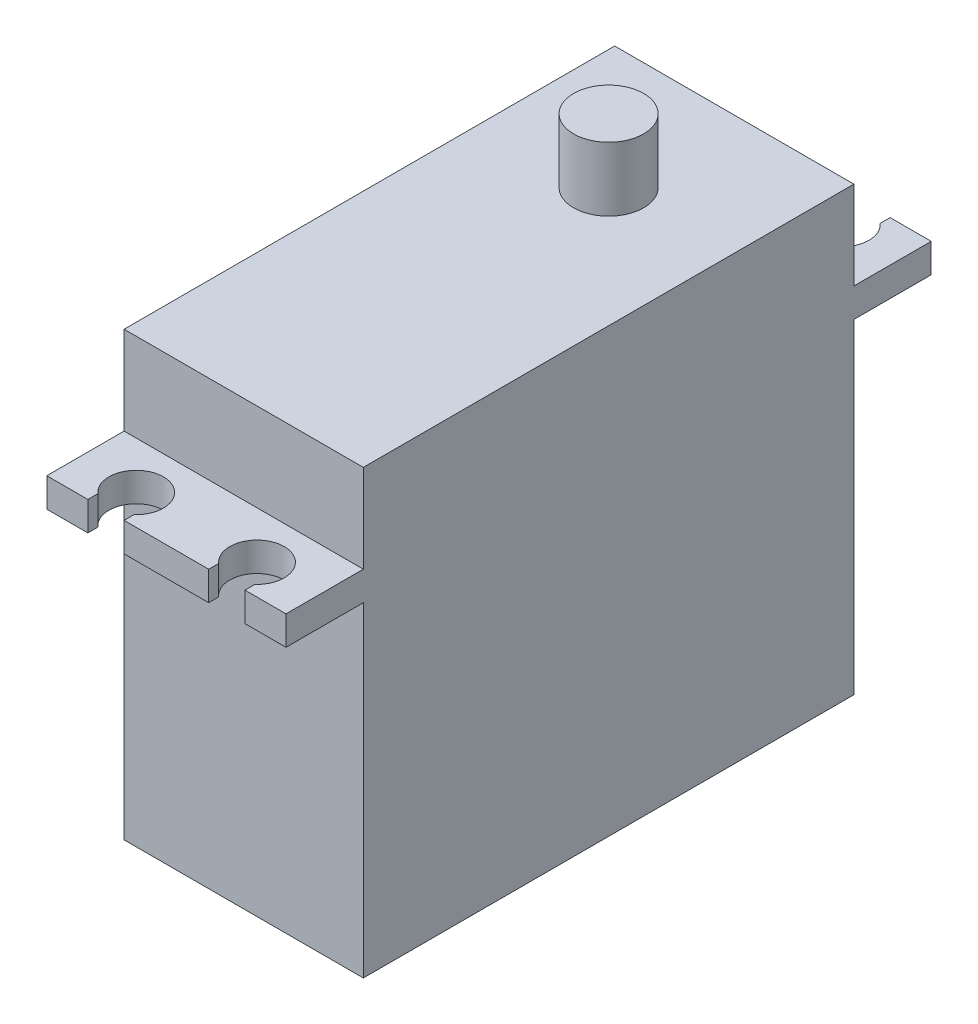
SolidWorks part; units mm, degrees
ref_plane "Front Plane" through (0, 0, 0) normal (0, 0, 1) x (1, 0, 0)
ref_plane "Top Plane" through (0, 0, 0) normal (0, 1, 0) x (1, 0, 0)
ref_plane "Right Plane" through (0, 0, 0) normal (1, 0, 0) x (0, 0, -1)
sketch "Sketch2" plane through (0, 0, 0) normal (1, 0, 0) x (0, 0, -1)
  line L1 (-20.3, 18.3) -> (20.3, 18.3)
  line L2 (-20.3, 18.3) -> (-20.3, -18.3)
  line L3 (-20.3, -18.3) -> (20.3, -18.3)
  line L4 (20.3, 18.3) -> (20.3, -18.3)
  line L5 (-20.3, 18.3) -> (20.3, -18.3) construction
  line L6 (-20.3, -18.3) -> (20.3, 18.3) construction
  line L7 (20.3, 11) -> (26.7, 11)
  line L8 (20.3, 11) -> (20.3, 8.6)
  line L9 (20.3, 8.6) -> (26.7, 8.6)
  line L10 (26.7, 11) -> (26.7, 8.6)
  line L11 (-20.3, 11) -> (-26.7, 11)
  line L12 (-20.3, 11) -> (-20.3, 8.6)
  line L13 (-20.3, 8.6) -> (-26.7, 8.6)
  line L14 (-26.7, 11) -> (-26.7, 8.6)
  line L16 (-26.7, 9.8) -> (26.7, 9.8) construction
  line L17 (7, 18.3) -> (12.8, 18.3)
  line L18 (7, 18.3) -> (7, 23.6)
  line L19 (7, 23.6) -> (12.8, 23.6)
  line L20 (12.8, 18.3) -> (12.8, 23.6)
  point P0 (0, 0)
  point P15 (9.9, 23.6)
  point P22 (0, 9.8)
  dimension "D1" = 26.9
  dimension "D2" = 40.6
  dimension "D3" = 5.3
  dimension "D4" = 53.4
  dimension "D5" = 36.6
  dimension "D6" = 2.4
  dimension "D7" = 5.8
  dimension "D8" = 10.4
extrude "Boss-Extrude1" add sketch "Sketch2" along normal blind 19.8 contours L4 L1 L2 L3 | L11 L14 L13 L2 | L1 L20 L19 L18 | L10 L7 L4 L9 region at (0, 0, 0) region at (0, 20.95, -9.9) region at (0, 9.8, 23.5) region at (0, 9.8, -23.5)
sketch "Sketch3" plane through (0, 18.3, 0) normal (0, 1, 0) x (1, 0, 0)
  line L0 (19.8, 12.8) -> (0, 12.8) construction
  line L1 (19.8, 7) -> (12.8, 7)
  line L2 (19.8, 7) -> (19.8, 12.8)
  line L3 (19.8, 12.8) -> (12.8, 12.8)
  line L4 (12.8, 7) -> (12.8, 12.8)
  line L5 (19.8, 12.8) -> (0, 12.8) construction
  line L6 (0, 7) -> (7, 7)
  line L7 (0, 7) -> (0, 12.8)
  line L8 (0, 12.8) -> (7, 12.8)
  line L9 (7, 7) -> (7, 12.8)
  line L10 (19.8, 26.7) -> (0, 26.7) construction
  line L11 (12.8, 12.8) -> (7, 12.8)
  line L12 (12.8, 7) -> (7, 7)
  circle A0 centre (9.9, 9.9) radius 2.9
  point P15 (7, 9.9)
  point P21 (9.9, 26.7)
  line M7 (19.8, 7) -> (0, 7)
extrude "Cut-Extrude1" cut sketch "Sketch3" along normal up to surface (5.3 mm away) contours A0 L4 M7 | A0 L4 L11 | A0 L11 L9 | A0 L9 L12 | L9 L8 L7 M7 | L4 L2 L3 M7 region at (16.3, 18.3, -9.9) region at (12.1522, 18.3, -7.6478) region at (12.1522, 18.3, -12.1522) region at (7.6478, 18.3, -7.6478) region at (7.6478, 18.3, -12.1522) region at (3.5, 18.3, -9.9) up to face at (9.9, 23.6, -9.9)
sketch "Sketch4" plane through (0, 11, 0) normal (0, 1, 0) x (1, 0, 0)
  line L0 (14.9, 24.2) -> (14.9, -24.2) construction
  line L1 (14.9, -24.2) -> (4.9, -24.2) construction
  line L2 (4.9, -24.2) -> (4.9, 24.2) construction
  line L3 (4.9, 24.2) -> (14.9, 24.2) construction
  line L4 (19.8, 26.7) -> (0, 26.7) construction
  line L5 (19.8, -20.3) -> (19.8, 20.3) construction
  line L6 (19.8, -26.7) -> (0, -26.7) construction
  line L7 (6.4, 26.7) -> (3.4, 26.7)
  line L8 (6.4, 26.7) -> (6.4, 25.8771)
  line L9 (6.4, 25.8771) -> (3.4, 25.8771)
  line L10 (3.4, 26.7) -> (3.4, 25.8771)
  line L11 (16.4, 26.7) -> (13.4, 26.7)
  line L12 (16.4, 26.7) -> (16.4, 25.8771)
  line L13 (16.4, 25.8771) -> (13.4, 25.8771)
  line L14 (13.4, 26.7) -> (13.4, 25.8771)
  line L15 (16.4, -26.7) -> (13.4, -26.7)
  line L16 (16.4, -26.7) -> (16.4, -25.8771)
  line L17 (16.4, -25.8771) -> (13.4, -25.8771)
  line L18 (13.4, -26.7) -> (13.4, -25.8771)
  line L20 (6.4, -26.7) -> (3.4, -26.7)
  line L21 (6.4, -26.7) -> (6.4, -25.8771)
  line L22 (6.4, -25.8771) -> (3.4, -25.8771)
  line L23 (3.4, -26.7) -> (3.4, -25.8771)
  circle A0 centre (14.9, 24.2) radius 2.25
  circle A1 centre (4.9, 24.2) radius 2.25
  circle A2 centre (14.9, -24.2) radius 2.25
  circle A3 centre (4.9, -24.2) radius 2.25
  point P8 (9.9, 24.2)
  point P11 (9.9, 26.7)
  point P13 (14.9, 0)
  point P16 (19.8, 0)
  line M8 (19.8, 26.7) -> (0, 26.7)
  dimension "D3" = 4.5
  dimension "D1" = 10
  dimension "D2" = 48.4
  dimension "D4" = 3
extrude "Cut-Extrude2" cut sketch "Sketch4" against normal through all contours L13 A0 | L13 A0 | A0 L12 L14 M8 | L9 A1 | L9 A1 | A1 L8 L10 M8 | L17 A2 | A2 L18 L15 L16 | L17 A2 | L22 A3 | A3 L23 L20 L21 | L22 A3 region at (4.9, 11, -26.4526) region at (14.9, 11, -26.4526) region at (4.9, 11, -24.0472) region at (4.9, 11, -26.1089) region at (14.9, 11, -26.1089) region at (14.9, 11, -24.0472) region at (14.9, 11, 26.4526) region at (14.9, 11, 26.1089) region at (14.9, 11, 24.0472) region at (4.9, 11, 26.4526) region at (4.9, 11, 26.1089) region at (4.9, 11, 24.0472)
